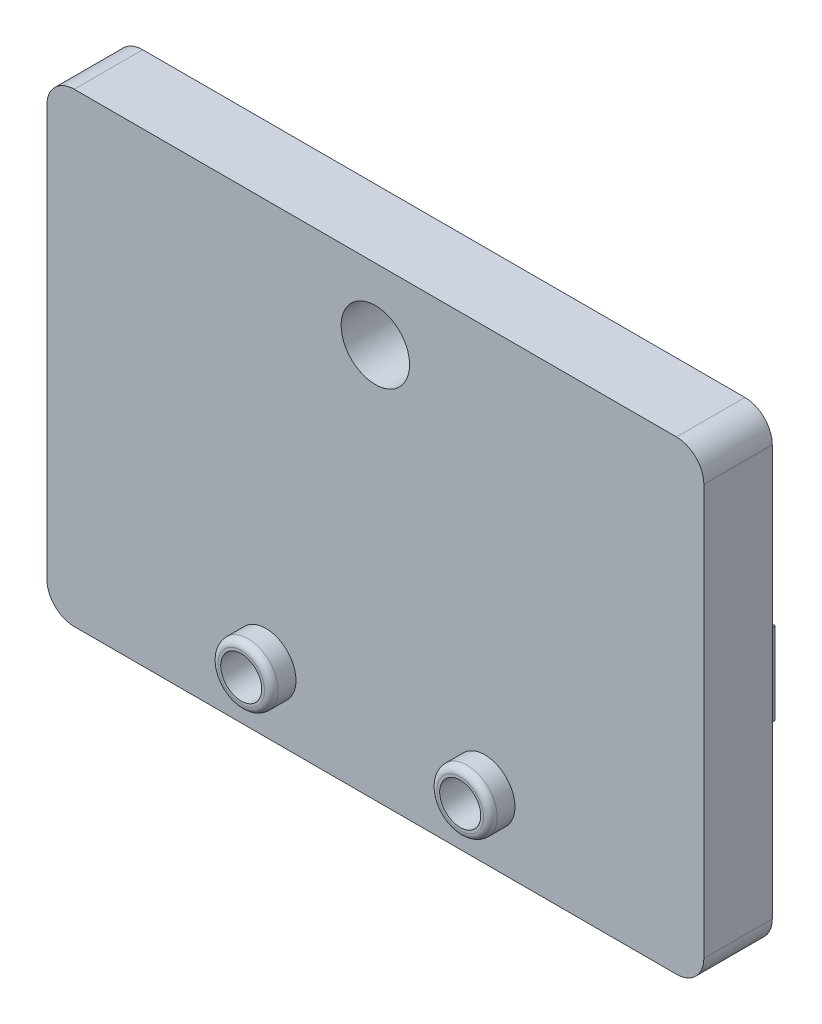
SolidWorks part; units mm, degrees
ref_plane "Front Plane" through (0, 0, 0) normal (0, 0, 1) x (1, 0, 0)
ref_plane "Top Plane" through (0, 0, 0) normal (0, 1, 0) x (1, 0, 0)
ref_plane "Right Plane" through (0, 0, 0) normal (1, 0, 0) x (0, 0, -1)
sketch "Sketch8" plane through (0, 0, 0) normal (0, 0, 1) x (1, 0, 0)
  line L1 (-33.5404, 119.8036) -> (10.4596, 119.8036)
  line L2 (-35.5404, 117.8036) -> (-35.5404, 87.8036)
  line L3 (-33.5404, 85.8036) -> (10.4596, 85.8036)
  line L4 (12.4596, 117.8036) -> (12.4596, 87.8036)
  line L5 (-35.5404, 119.8036) -> (12.4596, 85.8036) construction
  line L6 (-35.5404, 85.8036) -> (12.4596, 119.8036) construction
  arc A0 (10.4596, 85.8036) -> (12.4596, 87.8036) centre (10.4596, 87.8036) ccw
  arc A1 (10.4596, 119.8036) -> (12.4596, 117.8036) centre (10.4596, 117.8036) cw
  arc A2 (-35.5404, 87.8036) -> (-33.5404, 85.8036) centre (-33.5404, 87.8036) ccw
  arc A3 (-33.5404, 119.8036) -> (-35.5404, 117.8036) centre (-33.5404, 117.8036) ccw
  point P0 (-11.5404, 102.8036)
  dimension "D1" = 2
extrude "Boss-Extrude5" add sketch "Sketch8" along normal blind 5
sketch "Sketch9" plane through (0, 0, 5) normal (0, 0, 1) x (1, 0, 0)
  circle A9 centre (-3.5404, 90.4913) radius 1.5
  circle A10 centre (-3.5404, 90.4913) radius 2.2
  circle A13 centre (-19.5404, 90.4913) radius 1.5
  circle A14 centre (-19.5404, 90.4913) radius 2.2
extrude "Boss-Extrude11" add sketch "Sketch9" along normal blind 1.8 and the other way through all
extrude "Cut-Extrude4" cut sketch "Sketch9<10>" against normal through all contours A9 | A13
sketch "Sketch9<10>" plane through (0, 0, 5) normal (0, 0, 1) x (1, 0, 0) same geometry as "Sketch9"
sketch "Sketch11" plane through (0, 0, 0) normal (0, 0, -1) x (-1, 0, 0)
  line L1 (33.5404, 85.8036) -> (-10.4596, 85.8036) construction
  circle A0 centre (11.5404, 114.619) radius 2.5
  point P1 (11.5404, 85.8036)
extrude "Cut-Extrude5" cut sketch "Sketch11" against normal through all
sketch "Sketch12" plane through (0, 0, 0) normal (0, 0, -1) x (-1, 0, 0)
  line L1 (33.5404, 85.8036) -> (-10.4596, 85.8036) construction
  line L7 (-1.6693, 95.469) -> (-7.6693, 95.469)
  line L8 (29.8924, 95.469) -> (23.8924, 95.469)
  line L9 (29.8924, 95.469) -> (29.8924, 101.469)
  line L10 (29.8924, 101.469) -> (23.8924, 101.469)
  line L11 (23.8924, 95.469) -> (23.8924, 101.469)
  line L12 (29.8924, 95.469) -> (23.8924, 101.469) construction
  line L13 (29.8924, 101.469) -> (23.8924, 95.469) construction
  line L14 (-1.6693, 95.469) -> (-1.6693, 101.469)
  line L15 (-1.6693, 101.469) -> (-7.6693, 101.469)
  line L16 (-7.6693, 95.469) -> (-7.6693, 101.469)
  line L17 (-1.6693, 95.469) -> (-7.6693, 101.469) construction
  line L18 (-1.6693, 101.469) -> (-7.6693, 95.469) construction
  point P1 (11.5404, 85.8036)
  point P16 (26.8924, 98.469)
  point P17 (-4.6693, 98.469)
  point P22 (26.8924, 98.469)
  point P27 (-4.6693, 98.469)
extrude "Boss-Extrude12" add sketch "Sketch12" along normal blind 5
fillet "Fillet7" radius 0.5 2 edges at (-1.3404, 90.4913, 6.8) (-17.3404, 90.4913, 6.8)
